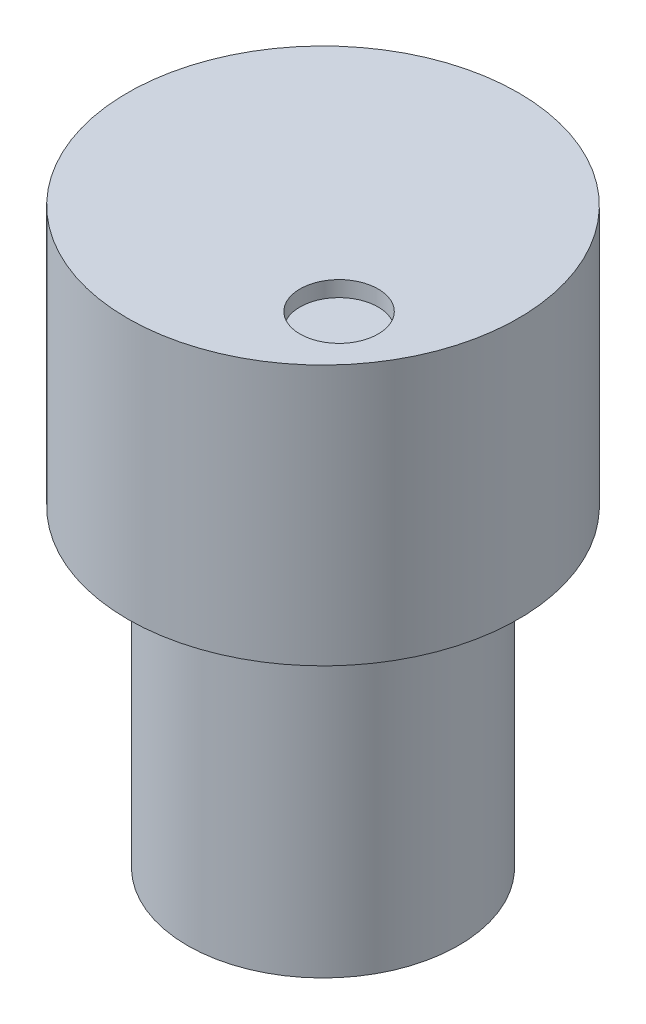
SolidWorks part; units mm, degrees
ref_plane "Front Plane" through (0, 0, 0) normal (0, 0, 1) x (1, 0, 0)
ref_plane "Top Plane" through (0, 0, 0) normal (0, 1, 0) x (1, 0, 0)
ref_plane "Right Plane" through (0, 0, 0) normal (1, 0, 0) x (0, 0, -1)
sketch "Sketch1" plane through (0, 0, 0) normal (0, 1, 0) x (1, 0, 0)
  circle A0 centre (0, 0) radius 3.2
  circle A1 centre (0, 0) radius 5.2
  dimension "D1" = 6.4
  dimension "D2" = 2
extrude "Boss-Extrude1" add sketch "Sketch1" along normal blind 12
sketch "Sketch2" plane through (0, 12, 0) normal (0, 1, 0) x (1, 0, 0)
  circle A0 centre (0, 0) radius 7.5
  dimension "D1" = 15
extrude "Boss-Extrude2" add sketch "Sketch2" along normal blind 10
sketch "Sketch4" plane through (0, 12, 0) normal (0, -1, 0) x (1, 0, 0)
  line L0 (-2.6458, -1.8) -> (2.6458, -1.8)
  circle A1 centre (0, 0) radius 3.2
  circle A2 centre (0, 0) radius 3.2
  circle A3 centre (0, 0) radius 3.2 construction
  point P7 (0, 3.4)
  circle M5 centre (0, 0) radius 3.2
  dimension "D2" = 5.2
  dimension "D1" = 0
extrude "Boss-Extrude4" add sketch "Sketch4" along normal blind 5 contours L0 M5 region at (0, 12, -2.372)
sketch "Sketch5" plane through (0, 22, 0) normal (0, 1, 0) x (1, 0, 0)
  line L0 (-2.6458, 1.8) -> (2.6458, 1.8) construction
  line L1 (-2.6458, 1.8) -> (2.6458, 1.8) construction
  line L2 (0, 1.8) -> (0, -7.5) construction
  line L3 (3.8302, -3.2139) -> (0, 0) construction
  circle A0 centre (3.8302, -3.2139) radius 1.5
  circle A1 centre (0, 0) radius 7.5 construction
  dimension "D3" = 3
  dimension "D1" = 310
  dimension "D2" = 5
extrude "Cut-Extrude1" cut sketch "Sketch5" against normal blind 0.6
